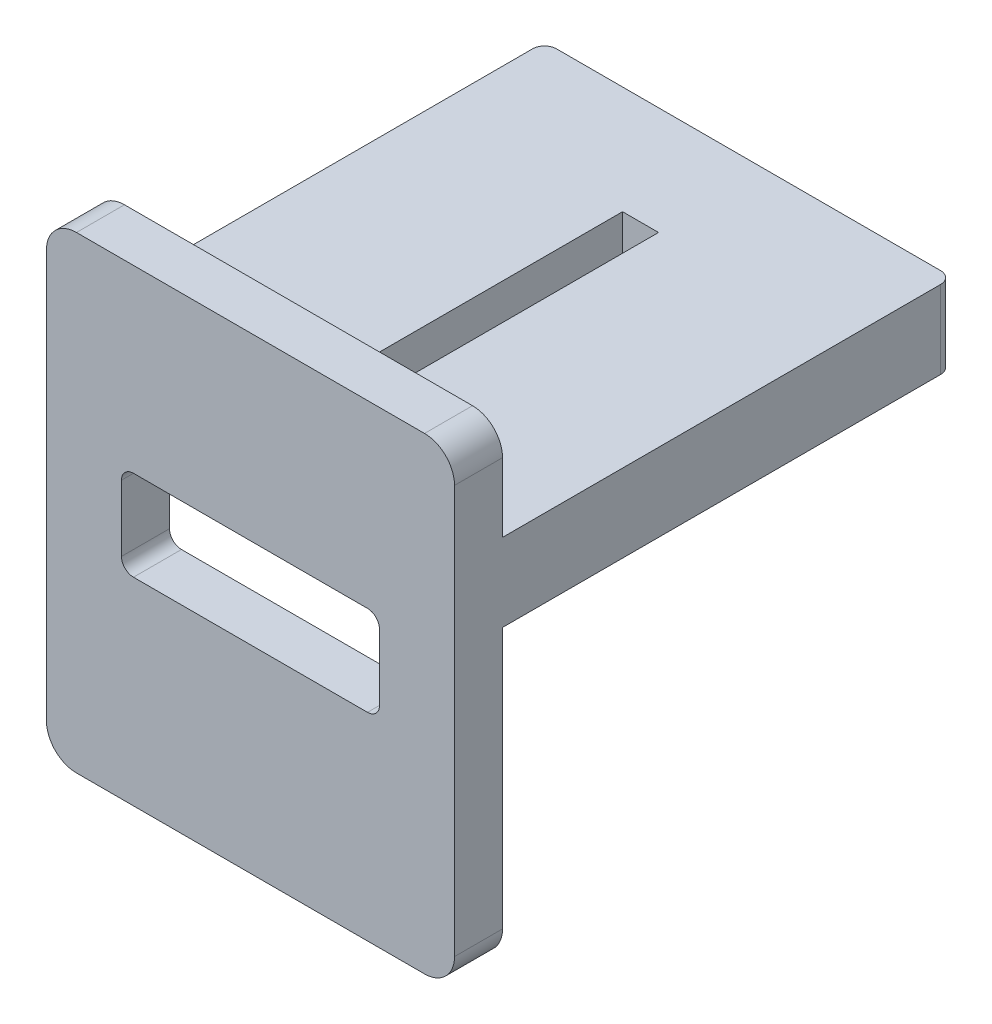
SolidWorks part; units mm, degrees
ref_plane "Front Plane" through (0, 0, 0) normal (0, 0, 1) x (1, 0, 0)
ref_plane "Top Plane" through (0, 0, 0) normal (0, 1, 0) x (1, 0, 0)
ref_plane "Right Plane" through (0, 0, 0) normal (1, 0, 0) x (0, 0, -1)
sketch "Sketch1" plane through (0, 0, 0) normal (0, 0, 1) x (1, 0, 0)
  line L1 (-34, 39) -> (34, 39)
  line L2 (-34, 39) -> (-34, -39)
  line L3 (-34, -39) -> (34, -39)
  line L4 (34, 39) -> (34, -39)
  line L5 (-34, 39) -> (34, -39) construction
  line L6 (-34, -39) -> (34, 39) construction
  point P0 (0, 0)
  dimension "D1" = 68
  dimension "D2" = 78
extrude "Boss-Extrude1" add sketch "Sketch1" along normal blind 8
sketch "Sketch2" plane through (0, 0, 0) normal (0, 0, -1) x (-1, 0, 0)
  line L0 (-34, -39) -> (-34, 39) construction
  line L1 (-34, 22.5) -> (34, 22.5)
  line L2 (-34, 22.5) -> (-34, 9.5)
  line L4 (34, 22.5) -> (34, 9.5)
  line L5 (34, 39) -> (34, -39) construction
  line L6 (-34, 22.5) -> (34, 9.5) construction
  line L7 (0, 16) -> (34, 16) construction
  line L8 (-34, 39) -> (34, 39) construction
  line L9 (-34, 9.5) -> (-19.5, 9.5)
  line L10 (-19.5, 9.5) -> (-19.5, 15.5)
  line L11 (-19.5, 15.5) -> (19.5, 15.5)
  line L12 (19.5, 15.5) -> (19.5, 9.5)
  line L13 (19.5, 9.5) -> (34, 9.5)
  dimension "D1" = 23
  dimension "D2" = 39
  dimension "D3" = 6
  dimension "D4" = 13
extrude "Boss-Extrude2" add sketch "Sketch2" along normal blind 75
sketch "Sketch3" plane through (0, 0, 8) normal (0, 0, 1) x (1, 0, 0)
  line L0 (34, 39) -> (-34, 39) construction
  line L1 (-21.5, 9) -> (21.5, 9)
  line L2 (-21.5, 9) -> (-21.5, -6)
  line L3 (-21.5, -6) -> (21.5, -6)
  line L4 (21.5, 9) -> (21.5, -6)
  line L5 (0, 39) -> (0, 9) construction
  dimension "D1" = 15
  dimension "D2" = 30
  dimension "D3" = 43
extrude "Cut-Extrude1" cut sketch "Sketch3" against normal up to next
fillet "Fillet1" radius 2 6 edges at (-21.5, -6, 4) (21.5, -6, 4) (21.5, 9, 4) (-21.5, 9, 4) (-34, 16, -75) (34, 16, -75)
fillet "Fillet2" radius 5 4 edges at (34, 39, 4) (34, -39, 4) (-34, -39, 4) (-34, 39, 4)
sketch "Sketch4" plane through (0, 22.5, 0) normal (0, 1, 0) x (1, 0, 0)
  line L0 (-32, 75) -> (32, 75) construction
  line L1 (-3, 57) -> (3, 57)
  line L2 (-3, 57) -> (-3, 12)
  line L3 (-3, 12) -> (3, 12)
  line L4 (3, 57) -> (3, 12)
  line L5 (0, 57) -> (0, 75) construction
  dimension "D1" = 6
  dimension "D2" = 45
  dimension "D3" = 18
extrude "Cut-Extrude2" cut sketch "Sketch4" against normal through all
